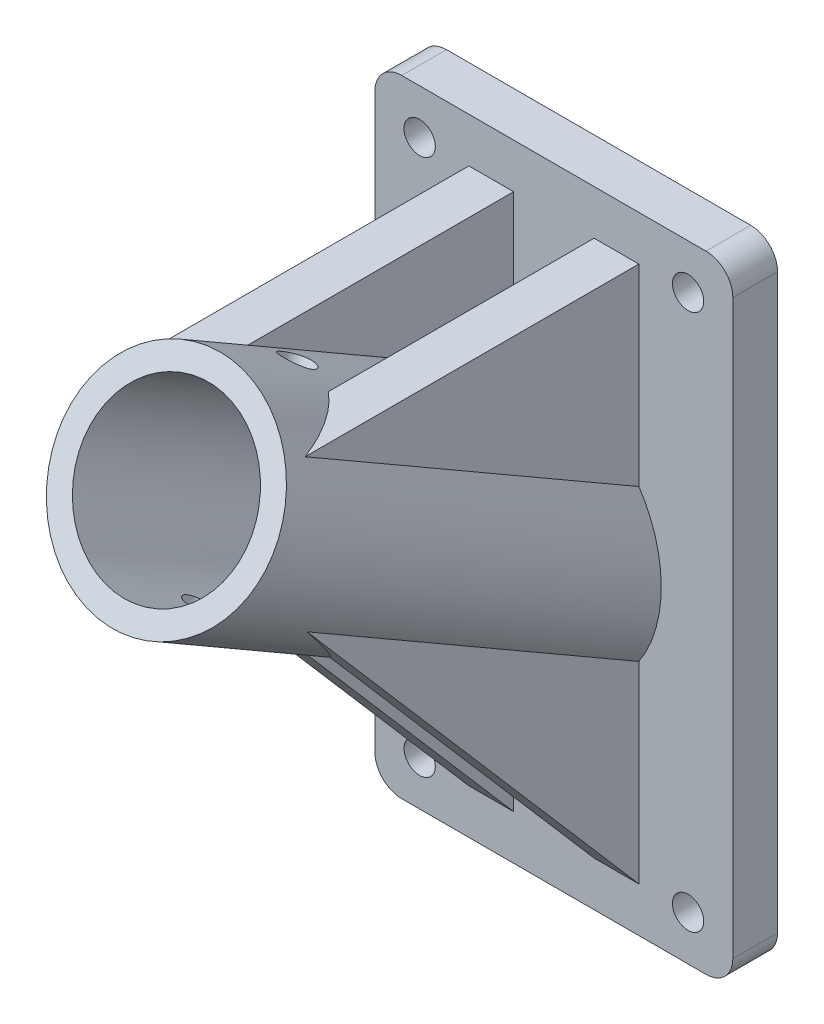
SolidWorks part; units mm, degrees
ref_plane "正面(Front)" through (0, 0, 0) normal (0, 0, 1) x (1, 0, 0)
ref_plane "平面(Top)" through (0, 0, 0) normal (0, 1, 0) x (1, 0, 0)
ref_plane "右側面(Right)" through (0, 0, 0) normal (1, 0, 0) x (0, 0, -1)
sketch "ｽｹｯﾁ1" plane through (0, 0, 0) normal (0, 0, 1) x (1, 0, 0)
  line L1 (-20, 35) -> (20, 35)
  line L2 (-20, 35) -> (-20, -35)
  line L3 (-20, -35) -> (20, -35)
  line L4 (20, 35) -> (20, -35)
  line L5 (-20, 35) -> (20, -35) construction
  line L6 (-20, -35) -> (20, 35) construction
  point P0 (0, 0)
  dimension "D1" = 70
  dimension "D2" = 40
extrude "ﾎﾞｽ - 押し出し1" add sketch "ｽｹｯﾁ1" against normal blind 5
ref_axis "軸1" through (-16.5, 0, 0) along (1, 0, 0)
ref_plane "平面1" through (0, 0, 0) normal (0, -0.5, -0.866) x (1, 0, 0)
sketch "ｽｹｯﾁ2" plane through (0, 0, 0) normal (0, -0.5, -0.866) x (1, 0, 0)
  circle A0 centre (0, 0) radius 12
  dimension "D1" = 24
extrude "ﾎﾞｽ - 押し出し2" add sketch "ｽｹｯﾁ2" along normal up to next from offset 50 offset against normal yes
sketch "ｽｹｯﾁ4" plane through (0, 0, -5) normal (0, 0, -1) x (-1, 0, 0)
  line L0 (-20, -35) -> (-20, 35) construction
  line L1 (-20, 35) -> (20, 35) construction
  line L2 (0, 0) -> (0, 48.7276) construction
  line L3 (0, 0) -> (30.1901, 0) construction
  circle A0 centre (-15, 30) radius 1.75
  circle A1 centre (15, 30) radius 1.75
  circle A2 centre (15, -30) radius 1.75
  circle A3 centre (-15, -30) radius 1.75
  dimension "D1" = 5
  dimension "D2" = 5
  dimension "D3" = 3.5
extrude "ｶｯﾄ - 押し出し1" cut sketch "ｽｹｯﾁ4" against normal up to next
fillet "ﾌｨﾚｯﾄ1" radius 3 4 edges at (20, 35, -2.5) (-20, 35, -2.5) (-20, -35, -2.5) (20, -35, -2.5)
sketch "ｽｹｯﾁ6" plane through (0, 0, 0) normal (1, 0, 0) x (0, 0, -1)
  line L0 (0, 30) -> (-38, 30)
  line L1 (0, -32) -> (0, 32) construction
  line L3 (-38, 30) -> (-38, 14)
  line L5 (-38, 14) -> (0, -30)
  line L6 (0, -30) -> (0, 30)
  line L7 (0, 35) -> (5, 35) construction
  line L8 (5, -35) -> (0, -35) construction
  dimension "D1" = 5
  dimension "D2" = 5
  dimension "D3" = 16
  dimension "D4" = 38
extrude "ﾎﾞｽ - 押し出し3" add sketch "ｽｹｯﾁ6" along normal mid plane 5 from offset 7
extrude "ﾎﾞｽ - 押し出し4" add sketch "ｽｹｯﾁ6<2>" along normal mid plane 5 from offset 7 offset against normal yes
sketch "ｽｹｯﾁ6<2>" plane through (0, 0, 0) normal (1, 0, 0) x (0, 0, -1) same geometry as "ｽｹｯﾁ6"
sketch "ｽｹｯﾁ5" plane through (0, 25, 43.3013) normal (0, 0.5, 0.866) x (1, 0, 0)
  circle A0 centre (0, 0) radius 9.4
  dimension "D1" = 18.8
extrude "ｶｯﾄ - 押し出し2" cut sketch "ｽｹｯﾁ5" against normal through all
ref_plane "平面2" through (0, 0, 0) normal (0, 0.866, -0.5) x (1, 0, 0)
sketch "ｽｹｯﾁ7" plane through (0, 0, 0) normal (0, 0.866, -0.5) x (1, 0, 0)
  line L0 (0, 0) -> (0, -54.301) construction
  line L1 (-9.4, -50) -> (9.4, -50) construction
  circle A0 centre (0, -20) radius 1.75
  circle A1 centre (0, -40) radius 1.75
  dimension "D1" = 3.5
  dimension "D2" = 10
  dimension "D3" = 20
extrude "ｶｯﾄ - 押し出し3" cut sketch "ｽｹｯﾁ7" against normal up to surface and the other way up to surface up to face at (0, 9.5499, 16.5409) other way up to face at (0, 9.5499, 16.5409)
